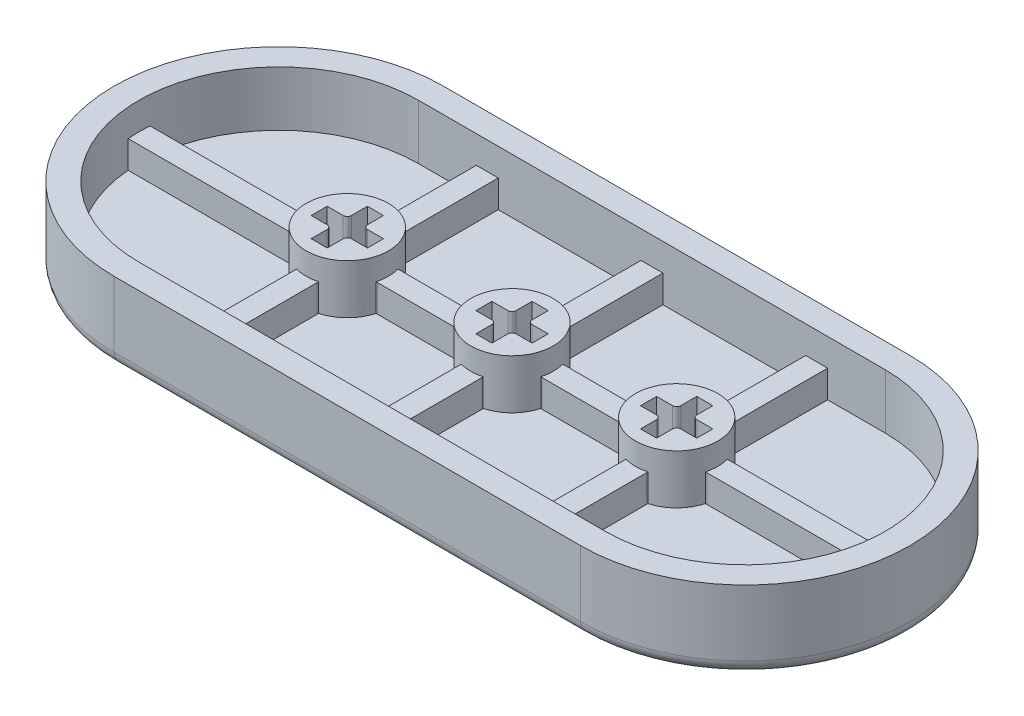
SolidWorks part; units mm, degrees
ref_plane "Front Plane" through (0, 0, 0) normal (0, 0, 1) x (1, 0, 0)
ref_plane "Top Plane" through (0, 0, 0) normal (0, 1, 0) x (1, 0, 0)
ref_plane "Right Plane" through (0, 0, 0) normal (1, 0, 0) x (0, 0, -1)
sketch "Sketch1" plane through (0, 0, 0) normal (0, 1, 0) x (1, 0, 0)
  line L0 (17, 0) -> (-17, 0) construction
  line L1 (17, -12) -> (-17, -12)
  line L2 (17, 12) -> (-17, 12)
  arc A1 (17, -12) -> (17, 12) centre (17, 0) ccw
  arc A2 (-17, 12) -> (-17, -12) centre (-17, 0) ccw
  point P5 (0, 0)
  point P10 (-29, 0)
  point P11 (29, 0)
  dimension "D2" = 12
  dimension "D3" = 58
extrude "button top" add sketch "Sketch1" along normal blind 1.8
sketch "Sketch2" plane through (0, 1.8, 0) normal (0, 1, 0) x (1, 0, 0)
  line L0 (-17, 0) -> (17, 0) construction
  line L1 (-17, 12) -> (17, 12)
  line L2 (-17, -12) -> (17, -12)
  line L3 (-17, 0) -> (17, 0) construction
  line L4 (-17, 10.2) -> (17, 10.2)
  line L5 (-17, -10.2) -> (17, -10.2)
  arc A2 (-17, 12) -> (-17, -12) centre (-17, 0) ccw
  arc A6 (17, -12) -> (17, 12) centre (17, 0) ccw
  arc A7 (17, -12) -> (17, 12) centre (17, 0) ccw construction
  arc A8 (-17, 10.2) -> (-17, -10.2) centre (-17, 0) ccw
  arc A9 (17, -10.2) -> (17, 10.2) centre (17, 0) ccw
  point P2 (0, 0)
  point P15 (0, 0)
  dimension "D1" = 1.8
extrude "button walls" add sketch "Sketch2" along normal blind 4
sketch "Sketch3" plane through (0, 1.8, 0) normal (0, 1, 0) x (1, 0, 0)
  line L0 (0, -2.05) -> (0, 2.05) construction
  line L1 (-2.05, 0) -> (2.05, 0) construction
  line L2 (-0.585, 0.885) -> (-0.585, 2.05)
  line L3 (-0.585, -2.05) -> (0.585, -2.05)
  line L4 (-0.585, -2.05) -> (-0.585, -0.885)
  line L5 (-0.585, 2.05) -> (0.585, 2.05)
  line L6 (0.585, -2.05) -> (0.585, -0.885)
  line L7 (-0.585, -2.05) -> (0.585, 2.05) construction
  line L8 (-0.585, 2.05) -> (0.585, -2.05) construction
  line L9 (-2.05, -0.585) -> (-0.885, -0.585)
  line L10 (-2.05, -0.585) -> (-2.05, 0.585)
  line L11 (-2.05, 0.585) -> (-0.885, 0.585)
  line L12 (2.05, -0.585) -> (2.05, 0.585)
  line L13 (-2.05, -0.585) -> (2.05, 0.585) construction
  line L14 (-2.05, 0.585) -> (2.05, -0.585) construction
  line L15 (0.885, 0.585) -> (2.05, 0.585)
  line L16 (0.585, 0.885) -> (0.585, 2.05)
  line L17 (0.885, -0.585) -> (2.05, -0.585)
  line L18 (11.415, 0.885) -> (11.415, 2.05)
  line L19 (11.415, -2.05) -> (12.585, -2.05)
  line L20 (11.415, -2.05) -> (11.415, -0.885)
  line L21 (11.415, 2.05) -> (12.585, 2.05)
  line L22 (12.585, -2.05) -> (12.585, -0.885)
  line L23 (9.95, -0.585) -> (11.115, -0.585)
  line L24 (9.95, -0.585) -> (9.95, 0.585)
  line L25 (9.95, 0.585) -> (11.115, 0.585)
  line L26 (14.05, -0.585) -> (14.05, 0.585)
  line L27 (12.885, 0.585) -> (14.05, 0.585)
  line L28 (12.585, 0.885) -> (12.585, 2.05)
  line L29 (12.885, -0.585) -> (14.05, -0.585)
  line L30 (12, -2.05) -> (12, 2.05) construction
  line L31 (9.95, 0) -> (14.05, 0) construction
  line L32 (11.415, -2.05) -> (12.585, 2.05) construction
  line L33 (11.415, 2.05) -> (12.585, -2.05) construction
  line L34 (9.95, -0.585) -> (14.05, 0.585) construction
  line L35 (9.95, 0.585) -> (14.05, -0.585) construction
  line L36 (-12.585, 0.885) -> (-12.585, 2.05)
  line L37 (-12.585, -2.05) -> (-11.415, -2.05)
  line L38 (-12.585, -2.05) -> (-12.585, -0.885)
  line L39 (-12.585, 2.05) -> (-11.415, 2.05)
  line L40 (-11.415, -2.05) -> (-11.415, -0.885)
  line L41 (-14.05, -0.585) -> (-12.885, -0.585)
  line L42 (-14.05, -0.585) -> (-14.05, 0.585)
  line L43 (-14.05, 0.585) -> (-12.885, 0.585)
  line L44 (-9.95, -0.585) -> (-9.95, 0.585)
  line L45 (-11.115, 0.585) -> (-9.95, 0.585)
  line L46 (-11.415, 0.885) -> (-11.415, 2.05)
  line L47 (-11.115, -0.585) -> (-9.95, -0.585)
  line L48 (-12, -2.05) -> (-12, 2.05) construction
  line L49 (-14.05, 0) -> (-9.95, 0) construction
  line L50 (-12.585, -2.05) -> (-11.415, 2.05) construction
  line L51 (-12.585, 2.05) -> (-11.415, -2.05) construction
  line L52 (-14.05, -0.585) -> (-9.95, 0.585) construction
  line L53 (-14.05, 0.585) -> (-9.95, -0.585) construction
  circle A0 centre (0, 0) radius 3
  arc A1 (-0.585, -0.885) -> (-0.885, -0.585) centre (-0.885, -0.885) ccw
  arc A2 (0.585, -0.885) -> (0.885, -0.585) centre (0.885, -0.885) cw
  arc A3 (0.885, 0.585) -> (0.585, 0.885) centre (0.885, 0.885) cw
  arc A4 (-0.585, 0.885) -> (-0.885, 0.585) centre (-0.885, 0.885) cw
  circle A5 centre (12, 0) radius 3
  arc A6 (11.415, -0.885) -> (11.115, -0.585) centre (11.115, -0.885) ccw
  arc A7 (12.585, -0.885) -> (12.885, -0.585) centre (12.885, -0.885) cw
  arc A8 (12.885, 0.585) -> (12.585, 0.885) centre (12.885, 0.885) cw
  arc A9 (11.415, 0.885) -> (11.115, 0.585) centre (11.115, 0.885) cw
  circle A10 centre (-12, 0) radius 3
  arc A11 (-12.585, -0.885) -> (-12.885, -0.585) centre (-12.885, -0.885) ccw
  arc A12 (-11.415, -0.885) -> (-11.115, -0.585) centre (-11.115, -0.885) cw
  arc A13 (-11.115, 0.585) -> (-11.415, 0.885) centre (-11.115, 0.885) cw
  arc A14 (-12.585, 0.885) -> (-12.885, 0.585) centre (-12.885, 0.885) cw
  point P6 (0, 0)
  point P9 (0, 0)
  point P22 (2.05, 0)
  point P24 (0, 2.05)
  point P29 (0.585, -0.585)
  point P32 (0.585, 0.585)
  point P40 (12, 0)
  point P43 (12, 0)
  point P69 (-12, 0)
  point P72 (-12, 0)
  dimension "D1" = 6
  dimension "D4" = 0.3
  dimension "D2" = 4.1
  dimension "D3" = 1.17
  dimension "D5" = 2
  dimension "D6" = 2
extrude "stem housing" add sketch "Sketch3" along normal blind 3.6
sketch "Sketch4" plane through (0, 1.8, 0) normal (0, 1, 0) x (1, 0, 0)
  line L0 (0, 3) -> (0, 10.2) construction
  line L1 (-0.8, 3) -> (-0.8, 10.2)
  line L2 (0.8, 3) -> (0.8, 10.2)
  line L3 (0, -3.19) -> (0, 3.19) construction
  line L6 (-15, 0) -> (-27.2, 0) construction
  line L9 (9, 0) -> (3, 0) construction
  line L12 (9, 0.8) -> (3, 0.8)
  line L15 (9, -0.8) -> (3, -0.8)
  line L18 (15, 0) -> (27.2, 0) construction
  line L19 (15, -0.8) -> (27.2, -0.8)
  line L20 (15, 0.8) -> (27.2, 0.8)
  line L21 (12, 3) -> (12, 10.2) construction
  line L22 (11.2, 3) -> (11.2, 10.2)
  line L23 (12.8, 3) -> (12.8, 10.2)
  line L24 (-12, 3) -> (-12, 10.2) construction
  line L25 (-12.8, 3) -> (-12.8, 10.2)
  line L26 (-11.2, 3) -> (-11.2, 10.2)
  line L27 (-15, -0.8) -> (-27.2, -0.8)
  line L28 (-15, 0.8) -> (-27.2, 0.8)
  line L29 (-3.19, 0) -> (3.19, 0) construction
  line L32 (-9, 0) -> (-3, 0) construction
  line L33 (-9, 0.8) -> (-3, 0.8)
  line L34 (-9, -0.8) -> (-3, -0.8)
  line L35 (0, -3) -> (0, -10.2) construction
  line L36 (-0.8, -3) -> (-0.8, -10.2)
  line L37 (0.8, -3) -> (0.8, -10.2)
  line L38 (12, -3) -> (12, -10.2) construction
  line L39 (11.2, -3) -> (11.2, -10.2)
  line L40 (12.8, -3) -> (12.8, -10.2)
  line L41 (-12, -3) -> (-12, -10.2) construction
  line L42 (-12.8, -3) -> (-12.8, -10.2)
  line L43 (-11.2, -3) -> (-11.2, -10.2)
  line L44 (17, 10.2) -> (-17, 10.2) construction
  circle A0 centre (0, 0) radius 3 construction
  circle A1 centre (0, 0) radius 3 construction
  arc A3 (-0.8, 3) -> (0.8, 3) centre (0, 3) ccw
  arc A4 (0.8, 10.2) -> (-0.8, 10.2) centre (0, 10.2) ccw
  arc A15 (9, 0.8) -> (9, -0.8) centre (9, 0) cw
  arc A16 (3, -0.8) -> (3, 0.8) centre (3, 0) cw
  arc A17 (15, -0.8) -> (15, 0.8) centre (15, 0) cw
  arc A18 (27.2, 0.8) -> (27.2, -0.8) centre (27.2, 0) cw
  arc A19 (11.2, 3) -> (12.8, 3) centre (12, 3) ccw
  arc A20 (12.8, 10.2) -> (11.2, 10.2) centre (12, 10.2) ccw
  arc A21 (-12.8, 3) -> (-11.2, 3) centre (-12, 3) ccw
  arc A22 (-11.2, 10.2) -> (-12.8, 10.2) centre (-12, 10.2) ccw
  circle A23 centre (-12, 0) radius 3 construction
  circle A24 centre (-12, 0) radius 3 construction
  arc A25 (-17, 10.2) -> (-17, -10.2) centre (-17, 0) ccw construction
  arc A26 (-15, -0.8) -> (-15, 0.8) centre (-15, 0) ccw
  arc A27 (-27.2, 0.8) -> (-27.2, -0.8) centre (-27.2, 0) ccw
  arc A33 (-9, 0.8) -> (-9, -0.8) centre (-9, 0) ccw
  arc A34 (-3, -0.8) -> (-3, 0.8) centre (-3, 0) ccw
  arc A35 (-0.8, -3) -> (0.8, -3) centre (0, -3) cw
  arc A36 (0.8, -10.2) -> (-0.8, -10.2) centre (0, -10.2) cw
  arc A37 (11.2, -3) -> (12.8, -3) centre (12, -3) cw
  arc A38 (12.8, -10.2) -> (11.2, -10.2) centre (12, -10.2) cw
  arc A39 (-12.8, -3) -> (-11.2, -3) centre (-12, -3) cw
  arc A40 (-11.2, -10.2) -> (-12.8, -10.2) centre (-12, -10.2) cw
  point P9 (0, 6.6)
  point P19 (6, 0)
  point P33 (21.1, 0)
  point P40 (12, 6.6)
  point P47 (-12, 6.6)
  point P55 (0, -6.6)
  point P59 (-21.1, 0)
  point P69 (12, -6.6)
  point P76 (-12, -6.6)
  point P81 (-6, 0)
  dimension "D1" = 1.6
  dimension "D3" = 2
  dimension "D4" = 12
  dimension "D5" = 12
  dimension "D2" = 2
extrude "Boss-Extrude4" add sketch "Sketch4" along normal blind 2
fillet "Fillet1" radius 1 4 edges at (0, 0, -12) (-29, 0, 0) (0, 0, 12) (29, 0, 0)
